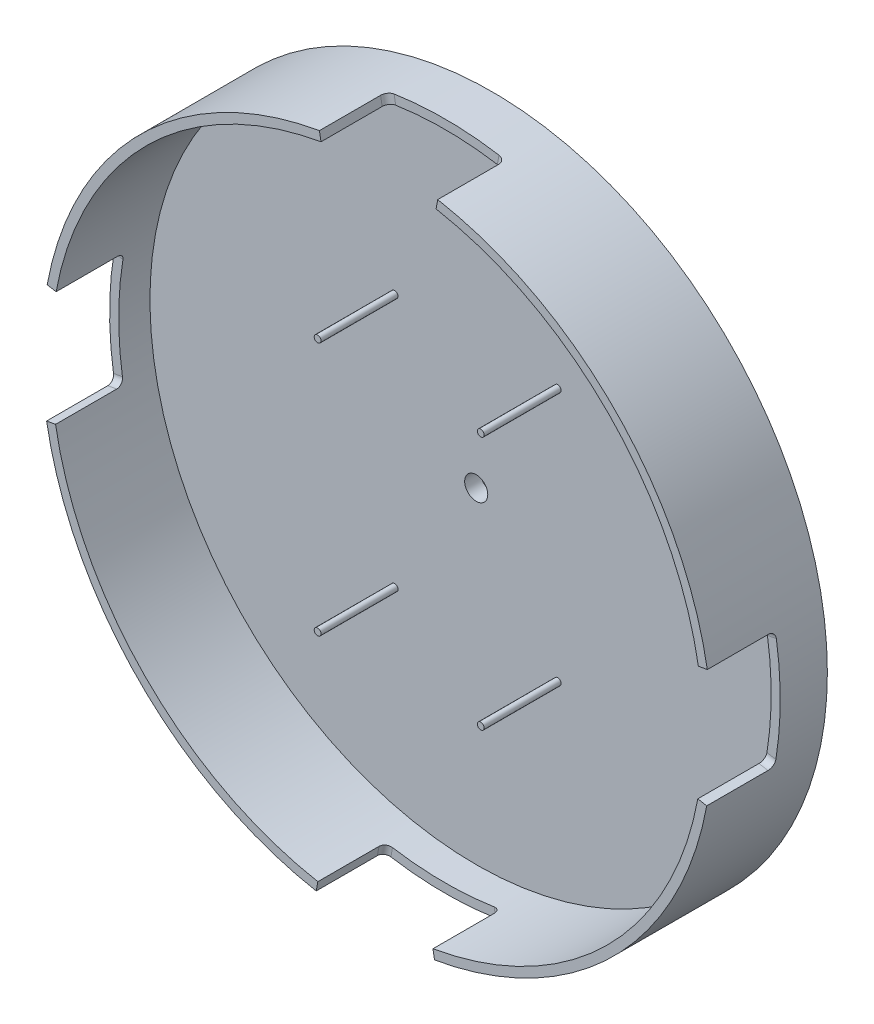
SolidWorks part; units mm, degrees
ref_plane "Front Plane" through (0, 0, 0) normal (0, 0, 1) x (1, 0, 0)
ref_plane "Top Plane" through (0, 0, 0) normal (0, 1, 0) x (1, 0, 0)
ref_plane "Right Plane" through (0, 0, 0) normal (1, 0, 0) x (0, 0, -1)
sketch "Sketch1" plane through (0, 0, 0) normal (0, 0, 1) x (1, 0, 0)
  circle A0 centre (0, 0) radius 74
  circle A1 centre (0, 0) radius 2.55
  dimension "D1" = 148
  dimension "D2" = 5.1
extrude "Boss-Extrude1" add sketch "Sketch1" along normal blind 3.5
sketch "Sketch2" plane through (0, 0, 0) normal (0, 0, 1) x (1, 0, 0)
  circle A0 centre (0, 0) radius 16
  circle A1 centre (0, 0) radius 32.5
  dimension "D1" = 65
  dimension "D2" = 32
extrude "Cut-Extrude4" cut sketch "Sketch2" along normal blind 1
fillet "Fillet1" radius 1.5 1 edges at (32.5, 0, 0)
fillet "Fillet2" radius 1.5 1 edges at (16, 0, 0)
sketch "Sketch3" plane through (0, 0, 0) normal (0, 0, 1) x (1, 0, 0)
  circle A0 centre (0, 0) radius 74
  circle A1 centre (0, 0) radius 72
  dimension "D1" = 148
  dimension "D2" = 2
extrude "Boss-Extrude2" add sketch "Sketch3" along normal blind 25.4
sketch "Sketch5" plane through (0, 0, 25.4) normal (0, 0, 1) x (1, 0, 0)
  line L0 (0, 0) -> (-12.3541, 70.9322) construction
  line L1 (-12.3541, 70.9322) -> (-12.6973, 72.9025)
  line L2 (0, 0) -> (13.0459, 70.8082) construction
  line L3 (13.0459, 70.8082) -> (13.4083, 72.7751)
  circle A0 centre (0, 0) radius 74 construction
  circle A1 centre (0, 0) radius 72 construction
  arc A2 (-12.3541, 70.9322) -> (13.0459, 70.8082) centre (0, 0) cw
  circle A3 centre (0, 0) radius 72 construction
  arc A4 (13.4083, 72.7751) -> (-12.6973, 72.9025) centre (0, 0) ccw
  dimension "D1" = 25.4
extrude "Cut-Extrude5" cut sketch "Sketch5" against normal blind 15
fillet "Fillet3" [suppressed] radius 1.5
pattern_circular "CirPattern2" count 4 over 360 about axis through (0, 0, 25.4) along (0, 0, 1) of "Cut-Extrude5"
fillet "Fillet4" radius 1.5 8 edges at (71.9174, 12.5257, 10.4) (71.7917, -13.2271, 10.4) (12.5257, -71.9174, 10.4) (-13.2271, -71.7917, 10.4) (-71.9174, -12.5257, 10.4) (-71.7917, 13.2271, 10.4) (-12.5257, 71.9174, 10.4) (13.2271, 71.7917, 10.4)
sketch "Sketch6" plane through (0, 0, 3.5) normal (0, 0, 1) x (1, 0, 0)
  line L1 (-20, -30) -> (20, -30) construction
  line L2 (-20, -30) -> (-20, 30) construction
  line L3 (-20, 30) -> (20, 30) construction
  line L4 (20, -30) -> (20, 30) construction
  line L5 (-20, -30) -> (20, 30) construction
  line L6 (-20, 30) -> (20, -30) construction
  circle A0 centre (18, 28) radius 0.75
  circle A1 centre (-18, 28) radius 0.75
  circle A2 centre (-18, -28) radius 0.75
  circle A3 centre (18, -28) radius 0.75
  point P0 (0, 0)
  point P10 (-16.1965, 27.25)
  dimension "D3" = 2
  dimension "D5" = 2
  dimension "D6" = 2
  dimension "D7" = 2
  dimension "D1" = 40
  dimension "D2" = 60
  dimension "D4" = 2
  dimension "D8" = 2
  dimension "D9" = 2
  dimension "D10" = 2
extrude "Boss-Extrude3" add sketch "Sketch6" along normal blind 17
